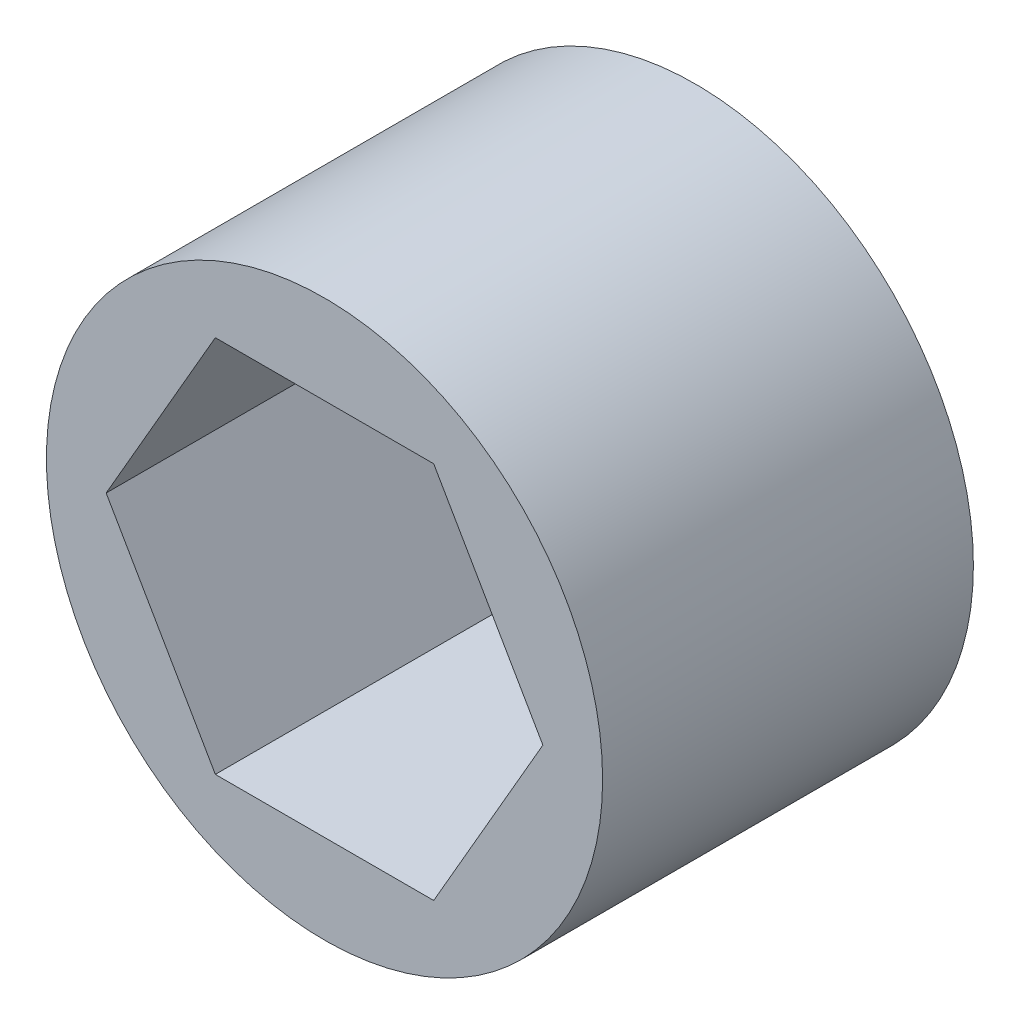
SolidWorks part; units mm, degrees
material "PET"
ref_plane "Front Plane" through (0, 0, 0) normal (0, 0, 1) x (1, 0, 0)
ref_plane "Top Plane" through (0, 0, 0) normal (0, 1, 0) x (1, 0, 0)
ref_plane "Right Plane" through (0, 0, 0) normal (1, 0, 0) x (0, 0, -1)
sketch "Sketch1" plane through (0, 0, 0) normal (0, 0, 1) x (1, 0, 0)
  line L7 (7.479, 0) -> (3.7395, 6.477)
  line L8 (3.7395, 6.477) -> (-3.7395, 6.477)
  line L9 (-3.7395, 6.477) -> (-7.479, 0)
  line L10 (-7.479, 0) -> (-3.7395, -6.477)
  line L11 (-3.7395, -6.477) -> (3.7395, -6.477)
  line L12 (3.7395, -6.477) -> (7.479, 0)
  circle A2 centre (0, 0) radius 6.477 construction
  circle A3 centre (0, 0) radius 9.525
  dimension "D1" = 19.05
  dimension "D2" = 12.954
extrude "Boss-Extrude1" add sketch "Sketch1" along normal mid plane 12.7
equation "\"D1@Boss-Extrude1\"=0.628445-0.132500+(0.008110/2)"
